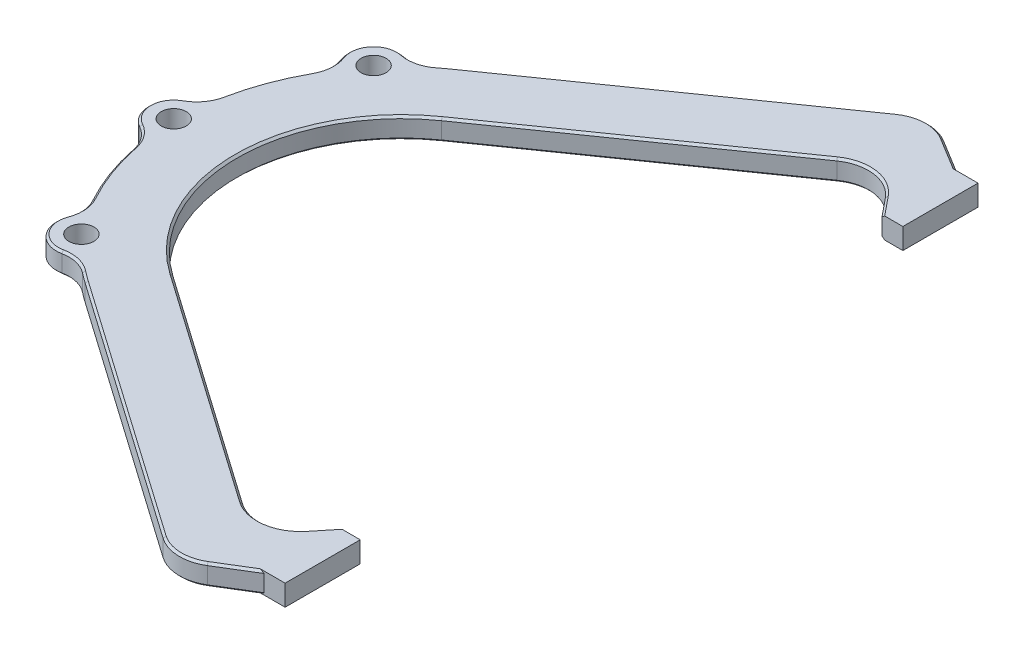
SolidWorks part; units mm, degrees
material "6061-T4 (SS)"
ref_plane "Front Plane" through (0, 0, 0) normal (0, 0, 1) x (1, 0, 0)
ref_plane "Top Plane" through (0, 0, 0) normal (0, 1, 0) x (1, 0, 0)
ref_plane "Right Plane" through (0, 0, 0) normal (1, 0, 0) x (0, 0, -1)
sketch "Sketch1" plane through (0, 0, 0) normal (0, 1, 0) x (1, 0, 0)
  line L0 (0, 0) -> (-54, 0) construction
  line L1 (0, 0) -> (-51.4201, 73.4355) construction
  line L2 (-30.9731, 44.2342) -> (31.2824, 87.826)
  line L3 (-22.0227, 32.1898) -> (33.6836, 71.1957)
  line L4 (50.6814, 83) -> (55.6814, 83)
  line L5 (55.6814, 83) -> (55.6814, 65)
  line L6 (55.6814, 65) -> (50.6814, 65)
  line L7 (50.6814, 65) -> (47.1814, 69.309)
  line L8 (-22.0227, -32.1898) -> (33.6836, -71.1957)
  line L9 (50.6814, 83) -> (42.2358, 88.1654)
  line L10 (-30.9731, -44.2342) -> (31.2824, -87.826)
  line L11 (50.6814, -83) -> (42.2358, -88.1654)
  line L12 (50.6814, -65) -> (47.1814, -69.309)
  line L13 (55.6814, -65) -> (50.6814, -65)
  line L14 (55.6814, -83) -> (55.6814, -65)
  line L15 (50.6814, -83) -> (55.6814, -83)
  arc A0 (-30.9731, 44.2342) -> (-33.3958, 42.4349) centre (0, 0) ccw
  circle A1 centre (-54, 0) radius 3
  arc A2 (42.2358, 88.1654) -> (31.2824, 87.826) centre (37.0182, 79.6345) ccw
  arc A3 (47.1814, 69.309) -> (33.6836, 71.1957) centre (39.4193, 63.0042) ccw
  arc A4 (-30.9731, -44.2342) -> (-33.3958, -42.4349) centre (0, 0) cw
  circle A5 centre (-41.1218, 35) radius 3
  arc A6 (-56.9048, 5.25) -> (-56.9048, -5.25) centre (-54, 0) ccw
  arc A7 (-39.931, 40.8807) -> (-46.7366, 32.8848) centre (-41.1218, 35) ccw
  arc A8 (-47.2264, 26.1852) -> (-46.7366, 32.8848) centre (-54.2229, 30.0645) ccw
  arc A9 (-39.931, 40.8807) -> (-33.3958, 42.4349) centre (-38.3434, 48.7215) ccw
  arc A10 (-56.9048, 5.25) -> (-52.9355, 10.6693) centre (-60.7778, 12.25) ccw
  arc A11 (-47.2264, 26.1852) -> (-52.9355, 10.6693) centre (0, 0) ccw
  circle A12 centre (-41.1218, -35) radius 3
  arc A13 (-39.931, -40.8807) -> (-33.3958, -42.4349) centre (-38.3434, -48.7215) cw
  arc A14 (-39.931, -40.8807) -> (-46.7366, -32.8848) centre (-41.1218, -35) cw
  arc A15 (-47.2264, -26.1852) -> (-46.7366, -32.8848) centre (-54.2229, -30.0645) cw
  arc A16 (-56.9048, -5.25) -> (-52.9355, -10.6693) centre (-60.7778, -12.25) cw
  arc A17 (-47.2264, -26.1852) -> (-52.9355, -10.6693) centre (0, 0) cw
  arc A18 (47.1814, -69.309) -> (33.6836, -71.1957) centre (39.4193, -63.0042) cw
  arc A19 (42.2358, -88.1654) -> (31.2824, -87.826) centre (37.0182, -79.6345) cw
  arc A20 (-22.0227, 32.1898) -> (-22.0227, -32.1898) centre (0.5169, 0) ccw
  dimension "D1" = 108
  dimension "D2" = 6
  dimension "D5" = 15
  dimension "D9" = 6
  dimension "D10" = 12
  dimension "D12" = 12
  dimension "D13" = 16
  dimension "D14" = 16
  dimension "D15" = 16
  dimension "D16" = 39.2965
  dimension "D18" = 10
  dimension "D19" = 10
  dimension "D3" = 55
  dimension "D4" = 76
  dimension "D6" = 3.5
  dimension "D7" = 65
  dimension "D8" = 18
  dimension "D11" = 35
  dimension "D17" = 5
  dimension "D20" = 9.9
extrude "Boss-Extrude1" add sketch "Sketch1" along normal mid plane 5
chamfer "Chamfer1" distance 0.5 angle 45 52 edges at (46.4586, 2.5, -85.5827) (36.7085, 2.5, -89.6297) (0.1547, 2.5, -66.0301) (-32.197, 2.5, -43.3515) (-36.4924, 2.5, -40.9386) (-45.6909, 2.5, -38.8889) (-46.2442, 2.5, -29.4811) (-50.6783, 2.5, -18.647) (-54.3238, 2.5, -7.5229) (-60, 2.5, 0) (-54.3238, 2.5, 7.5229) (-50.6783, 2.5, 18.647) (-46.2442, 2.5, 29.4811) (-45.6909, 2.5, 38.8889) (-36.4924, 2.5, 40.9386) (46.4586, 2.5, 85.5827) (-32.197, 2.5, 43.3515) (36.7085, 2.5, 89.6297) (0.1547, 2.5, 66.0301) (-45.6909, -2.5, -38.8889) (-46.2442, -2.5, -29.4811) (-50.6783, -2.5, -18.647) (-54.3238, -2.5, -7.5229) (-60, -2.5, 0) (-54.3238, -2.5, 7.5229) (-50.6783, -2.5, 18.647) (-46.2442, -2.5, 29.4811) (-45.6909, -2.5, 38.8889) (-36.4924, -2.5, 40.9386) (-32.197, -2.5, 43.3515) (0.1547, -2.5, 66.0301) (36.7085, -2.5, 89.6297) (46.4586, -2.5, 85.5827) (48.9314, -2.5, 67.1545) (40.8037, -2.5, 72.9079) (5.8305, -2.5, 51.6927) (-38.7796, -2.5, 0) (5.8305, -2.5, -51.6927) (40.8037, -2.5, -72.9079) (48.9314, -2.5, -67.1545) (46.4586, -2.5, -85.5827) (36.7085, -2.5, -89.6297) (0.1547, -2.5, -66.0301) (-32.197, -2.5, -43.3515) (-36.4924, -2.5, -40.9386) (48.9314, 2.5, 67.1545) (40.8037, 2.5, 72.9079) (5.8305, 2.5, 51.6927) (48.9314, 2.5, -67.1545) (-38.7796, 2.5, 0) (40.8037, 2.5, -72.9079) (5.8305, 2.5, -51.6927)
